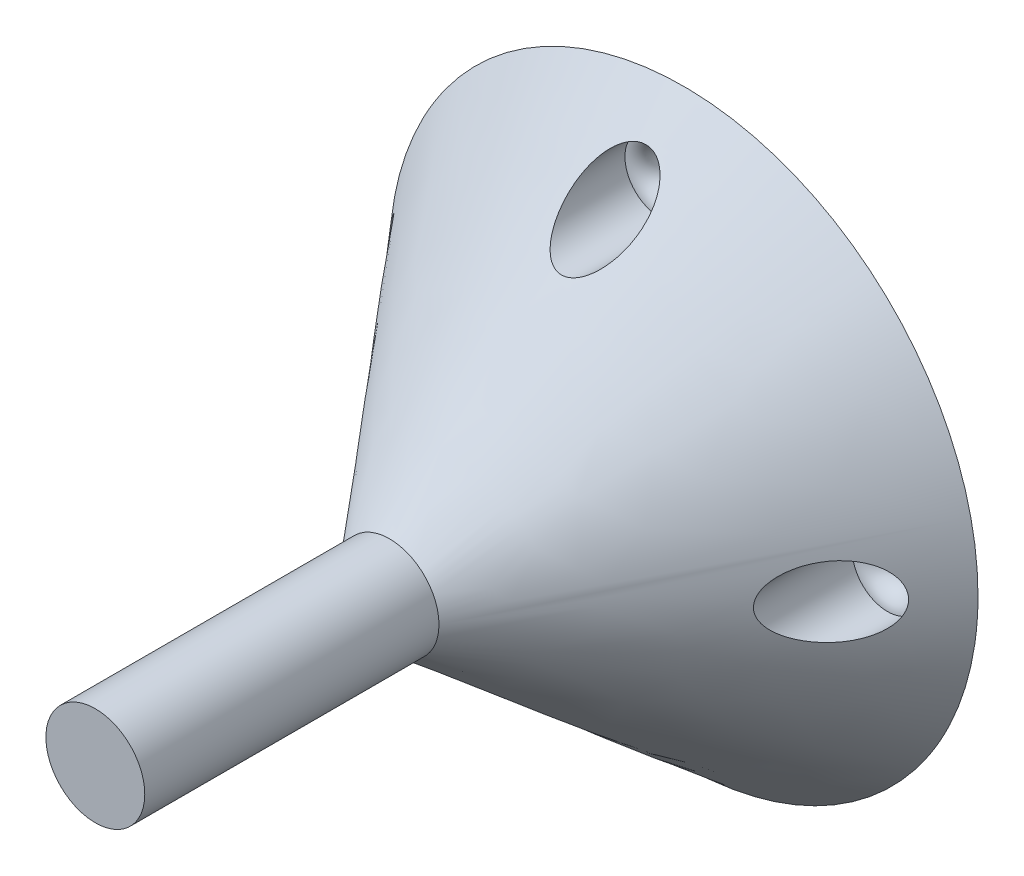
SolidWorks part; units mm, degrees
ref_plane "Piano frontale" through (0, 0, 0) normal (0, 0, 1) x (1, 0, 0)
ref_plane "Piano superiore" through (0, 0, 0) normal (0, 1, 0) x (1, 0, 0)
ref_plane "Piano destro" through (0, 0, 0) normal (1, 0, 0) x (0, 0, -1)
sketch "Schizzo1" plane through (0, 0, 0) normal (0, 0, 1) x (1, 0, 0)
  circle A0 centre (0, 0) radius 25
  dimension "D1" = 50
ref_plane "Piano1" through (0, 0, 25) normal (0, 0, 1) x (1, 0, 0)
sketch "Schizzo2" plane through (0, 0, 25) normal (0, 0, 1) x (1, 0, 0)
  circle A0 centre (0, 0) radius 4.2
  dimension "D1" = 8.4
loft "Loft1" add profiles "Schizzo1", "Schizzo2" connector at (-24.2224, 6.1868, 0) connector at (-3.7422, 1.9068, 25)
sketch "Schizzo3" plane through (0, 0, 25) normal (0, 0, 1) x (1, 0, 0)
  circle A0 centre (0, 0) radius 4.2
extrude "Estrusione-Estrusione1" add sketch "Schizzo3" along normal blind 25
sketch "Schizzo4" plane through (0, 0, 25) normal (0, 0, 1) x (1, 0, 0)
  line L0 (0, 0) -> (37.31, 0) construction
  line L1 (0, 0) -> (0, -28.2252) construction
  circle A0 centre (0, 19.3147) radius 1.6
  circle A1 centre (19.3147, 0) radius 1.6
  circle A2 centre (0, -19.3147) radius 1.6
  circle A3 centre (-19.3147, 0) radius 1.6
  point P15 (0, 0)
  dimension "D1" = 3.2
  dimension "D2" = 4
extrude "Taglio-Estrusione1" cut sketch "Schizzo4" against normal blind 25
sketch "Schizzo5" plane through (0, 0, 25) normal (0, 0, 1) x (1, 0, 0)
  circle A0 centre (0, 19.3147) radius 3
  circle A1 centre (19.3147, 0) radius 3
  circle A2 centre (0, -19.3147) radius 3
  circle A3 centre (-19.3147, 0) radius 3
  point P12 (0, 0)
  dimension "D1" = 6
  dimension "D2" = 4
extrude "Taglio-Estrusione2" cut sketch "Schizzo5" against normal blind 23
fillet "Raccordo1" radius 1.5 1 edges at (-17.7147, 0, 2)
fillet "Raccordo2" radius 1.5 1 edges at (1.6, 19.3147, 2)
fillet "Raccordo3" radius 1.5 1 edges at (20.9147, 0, 2)
fillet "Raccordo4" radius 1.5 1 edges at (1.6, -19.3147, 2)
